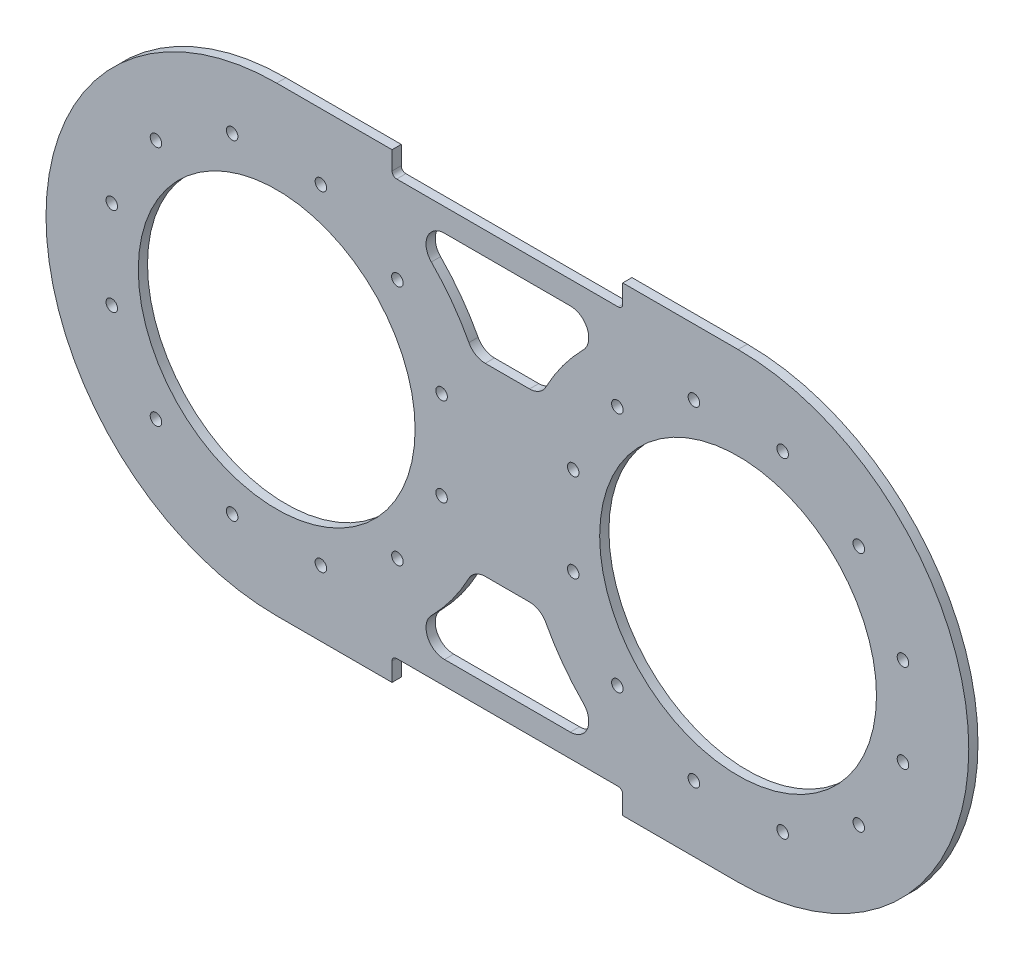
SolidWorks part; units mm, degrees
ref_plane "前视基准面" through (0, 0, 0) normal (0, 0, 1) x (1, 0, 0)
ref_plane "上视基准面" through (0, 0, 0) normal (0, 1, 0) x (1, 0, 0)
ref_plane "右视基准面" through (0, 0, 0) normal (1, 0, 0) x (0, 0, -1)
sketch "草图1" plane through (0, 0, 0) normal (0, 0, 1) x (1, 0, 0)
  line L5 (55, 0) -> (-55, 0) construction
  line L8 (-25, 45) -> (25, 45)
  line L9 (-7.28, -20) -> (7.28, -20)
  line L10 (-25, 45) -> (-25, 50)
  line L11 (-50, 50) -> (-25, 50)
  line L12 (25, 40) -> (-25, 40)
  line L13 (-7.28, 20) -> (7.28, 20)
  line L14 (25, -40) -> (-25, -40)
  line L15 (-25, -45) -> (25, -45)
  line L16 (-25, -45) -> (-25, -50)
  line L17 (-50, -50) -> (-25, -50)
  line L18 (0, -55) -> (0, 55) construction
  line L19 (50, -50) -> (25, -50)
  line L20 (25, -45) -> (25, -50)
  line L21 (25, 45) -> (25, 50)
  line L22 (50, 50) -> (25, 50)
  arc A2 (50, 50) -> (50, -50) centre (50, 0) cw
  arc A3 (-50, 50) -> (-50, -50) centre (-50, 0) ccw
  circle A4 centre (-50, 0) radius 30
  circle A5 centre (50, 0) radius 30
  arc A12 (-25, 40) -> (-7.28, 20) centre (-50, 0) cw
  arc A13 (-25, -40) -> (-7.28, -20) centre (-50, 0) ccw
  arc A14 (25, -40) -> (7.28, -20) centre (50, 0) cw
  arc A15 (25, 40) -> (7.28, 20) centre (50, 0) ccw
  point P29 (0, -45)
  point P30 (0, -40)
  point P31 (0, -20)
  point P32 (0, 20)
  point P33 (0, 40)
  point P34 (0, 45)
extrude "凸台-拉伸1" add sketch "草图1" along normal blind 2
hole_wizard "M3 螺纹孔的螺纹孔钻头1" positions "3D草图1" profile "草图2" hole size "M3" standard "ISO" end condition through all
sketch3d "3D草图1"
  point P182 (-40.4237, 35.7393, 2)
  point P184 (-23.837, 26.163, 2)
  point P186 (-14.2607, 9.5763, 2)
  point P211 (-59.6568, 35.7176, 2)
  point P213 (-76.163, 26.163, 2)
  point P215 (-85.7393, 9.5763, 2)
  point P220 (85.7393, 9.5763, 2)
  point P221 (76.163, 26.163, 2)
  point P222 (59.6568, 35.7176, 2)
  point P223 (14.2607, 9.5763, 2)
  point P224 (23.837, 26.163, 2)
  point P225 (40.4237, 35.7393, 2)
  point P226 (40.4237, -35.7393, 2)
  point P227 (23.837, -26.163, 2)
  point P228 (14.2607, -9.5763, 2)
  point P229 (59.6568, -35.7176, 2)
  point P230 (76.163, -26.163, 2)
  point P231 (85.7393, -9.5763, 2)
  point P232 (-85.7393, -9.5763, 2)
  point P233 (-76.163, -26.163, 2)
  point P234 (-59.6568, -35.7176, 2)
  point P235 (-14.2607, -9.5763, 2)
  point P236 (-23.837, -26.163, 2)
  point P237 (-40.4237, -35.7393, 2)
sketch "草图2" plane through (-40.4237, 35.7393, 2) normal (1, 0, 0) x (0, -1, 0)
  line L0 (0, 0) -> (0, 2)
  line L1 (0, 2) -> (1.25, 2)
  line L2 (1.25, 2) -> (1.25, 0)
  line L5 (1.25, 0) -> (0, 0)
  line L11 (0, -6.35) -> (0, 107.95) construction
  dimension "通孔孔直径" = 2.5
  dimension "通孔孔深度" = 2
fillet "圆角1" radius 4 8 edges at (7.28, 20, 1) (-7.28, 20, 1) (25, 40, 1) (-25, 40, 1) (-7.28, -20, 1) (7.28, -20, 1) (25, -40, 1) (-25, -40, 1)
fillet "圆角2" radius 1 4 edges at (25, 45, 1) (-25, 45, 1) (25, -45, 1) (-25, -45, 1)
